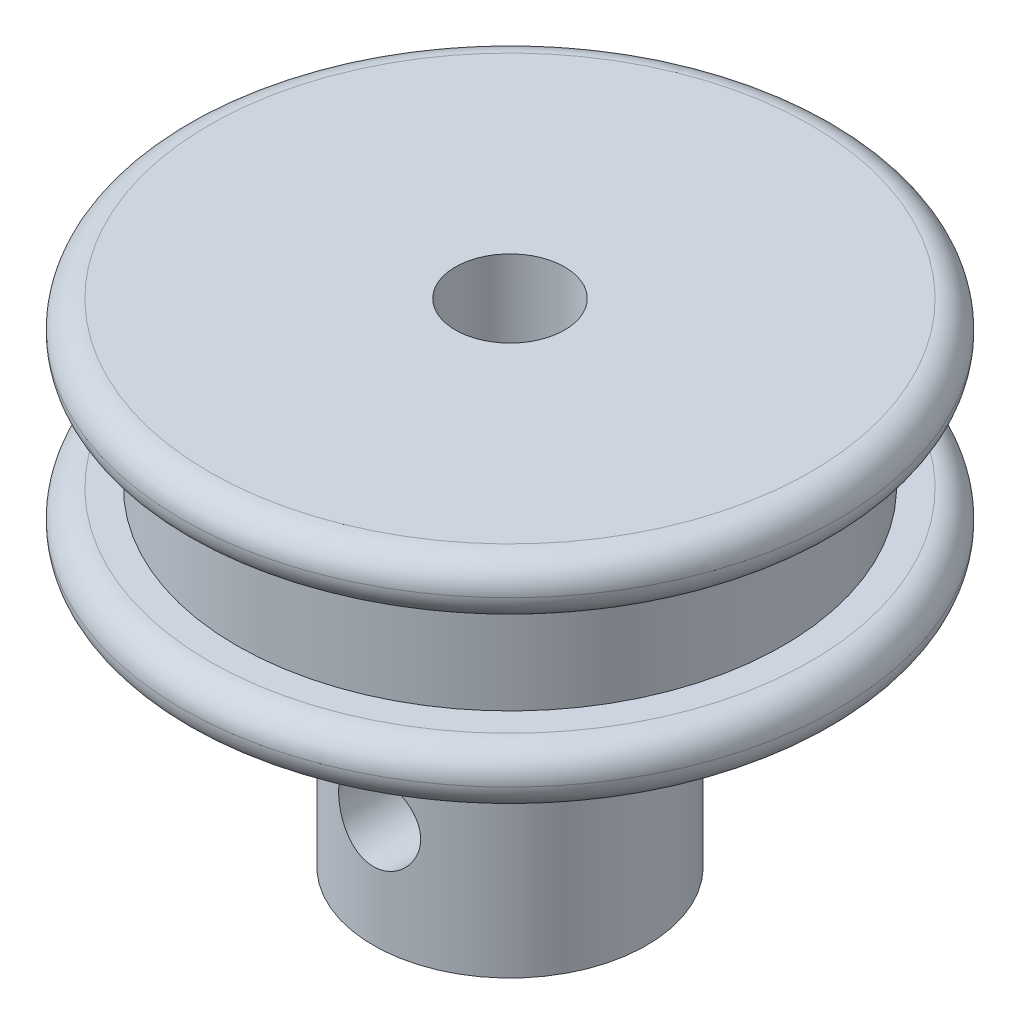
SolidWorks part; units mm, degrees
ref_plane "前视基准面" through (0, 0, 0) normal (0, 0, 1) x (1, 0, 0)
ref_plane "上视基准面" through (0, 0, 0) normal (0, 1, 0) x (1, 0, 0)
ref_plane "右视基准面" through (0, 0, 0) normal (1, 0, 0) x (0, 0, -1)
other "Configuration Table"
sketch "草图1" plane through (0, 0, 0) normal (0, 1, 0) x (1, 0, 0)
  circle A0 centre (0, 0) radius 10
  dimension "D1" = 20
extrude "凸台-拉伸1" add sketch "草图1" along normal blind 4
sketch "草图2" plane through (0, 4, 0) normal (0, 1, 0) x (1, 0, 0)
  circle A0 centre (0, 0) radius 12
  dimension "D1" = 24
extrude "凸台-拉伸2" add sketch "草图2" along normal blind 2
sketch "草图3" plane through (0, 0, 0) normal (0, -1, 0) x (1, 0, 0)
  circle A0 centre (0, 0) radius 12
  dimension "D1" = 24
extrude "凸台-拉伸3" add sketch "草图3" along normal blind 2
sketch "草图4" plane through (0, -2, 0) normal (0, -1, 0) x (-1, 0, 0)
  circle A0 centre (0, 0) radius 5
extrude "凸台-拉伸4" add sketch "草图4" along normal blind 10
sketch "草图5" plane through (0, -12, 0) normal (0, -1, 0) x (1, 0, 0)
  circle A0 centre (0, 0) radius 2
extrude "切除-拉伸1" cut sketch "草图5" against normal through all
fillet "圆角2" radius 1 4 edges at (0, 0, -12) (0, 4, 12) (0, 6, 12) (0, -2, -12)
sketch "草图6" plane through (0, 0, 0) normal (0, 0, 1) x (1, 0, 0)
  line L0 (-5, -12) -> (5, -12) construction
  circle A0 centre (0, -8) radius 1.5
  dimension "D2" = 3
  dimension "D1" = 4
extrude "切除-拉伸2" cut sketch "草图6" along normal blind 10 and the other way blind 10
